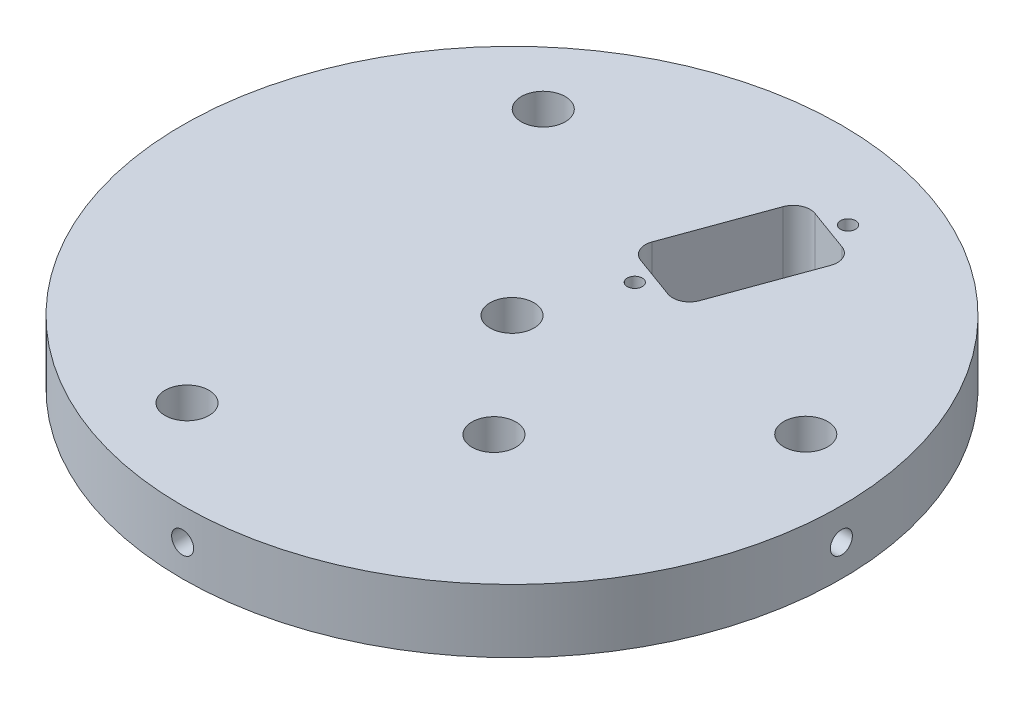
SolidWorks part; units mm, degrees
material "6061-T6 (SS)"
ref_plane "Front Plane" through (0, 0, 0) normal (0, 0, 1) x (1, 0, 0)
ref_plane "Top Plane" through (0, 0, 0) normal (0, 1, 0) x (1, 0, 0)
ref_plane "Right Plane" through (0, 0, 0) normal (1, 0, 0) x (0, 0, -1)
sketch "Sketch1" plane through (0, 0, 0) normal (0, 1, 0) x (1, 0, 0)
  line L0 (0, 0) -> (-50.3682, 60.0265)
  line L1 (0, 0) -> (50.3682, 60.0265)
  line L2 (0, 0) -> (0, 72.1431) construction
  circle A0 centre (0, 0) radius 78.359
  circle A1 centre (0, 0) radius 51.1048
  circle A2 centre (0, 0) radius 76.1746
  dimension "D1" = 156.718
  dimension "D2" = 102.2096
  dimension "D3" = 152.3492
  dimension "D4" = 80
extrude "Boss-Extrude1" add sketch "Sketch1" along normal blind 25.4 contours L2 A2 L1 A0 | L2 A1 L1 A2 | L2 A2 L1 A1 | L2 A0 L1 A2 | A2 L2 A1 L0 | A0 L2 A2 L0 | A2 L2 A0 L0 | A1 L2 A2 L0 region at (-22.4568, 0, 48.1587) region at (-40.1048, 0, -49.4238) region at (-33.0764, 0, 70.9325) region at (-48.8794, 0, -59.85)
ref_plane "Plane1" through (0, 12.7, 0) normal (0, 1, 0) x (1, 0, 0)
sketch "Sketch6" plane through (0, 25.4, 0) normal (0, 1, 0) x (1, 0, 0)
  circle A0 centre (0, 0) radius 49.5173
  dimension "D1" = 99.0346
extrude "Boss-Extrude5" add sketch "Sketch6" along normal blind 9.525
sketch "Sketch7" plane through (0, 0, 0) normal (0, -1, 0) x (1, 0, 0)
  circle A0 centre (0, 0) radius 49.5173
  dimension "D1" = 99.0346
extrude "Boss-Extrude6" add sketch "Sketch7" along normal blind 9.525
sketch "Sketch8" plane through (0, -9.525, 0) normal (0, -1, 0) x (1, 0, 0)
  circle A0 centre (0, 0) radius 46.99
  dimension "D1" = 93.98
ref_plane "Plane2" through (0, 0, -49.5173) normal (0, 0, -1) x (-1, 0, 0)
ref_plane "Plane5" through (0, 25.4, 0) normal (0, 1, 0) x (1, 0, 0)
ref_axis "Axis1" through (0, 0, 0) along (0, 1, 0)
ref_plane "Plane3" through (0, 34.925, 0) normal (0, 1, 0) x (1, 0, 0)
sketch "Sketch9" plane through (0, 34.925, 0) normal (0, 1, 0) x (1, 0, 0)
  line L0 (0, 0) -> (-26.8004, -73.6334) construction
  line L1 (0, 0) -> (32.0596, -38.2071) construction
  line L2 (0, 0) -> (0, -86.0416) construction
  circle A0 centre (0, 0) radius 3.3
  circle A1 centre (-13.031, -35.8023) radius 3.3
  circle A4 centre (14.1499, -16.8632) radius 3.3
  circle A5 centre (-24.4902, 29.1863) radius 3.3
  circle A6 centre (37.5212, 6.616) radius 3.3
  point P15 (-1.3039, -1.0954)
  point P18 (0, 0)
  dimension "D1" = 6.6
  dimension "D2" = 6.6
  dimension "D6" = 6.6
  dimension "D3" = 38.1
  dimension "D4" = 60
  dimension "D7" = 22.0133
  dimension "D8" = 20
extrude "Cut-Extrude6" cut sketch "Sketch9" against normal through all
sketch "Sketch10" plane through (0, 25.4, 0) normal (0, 1, 0) x (1, 0, 0)
  circle A0 centre (0, 0) radius 82.3228
extrude "Cut-Extrude7" cut sketch "Sketch10" against normal through all
hole_wizard "Tap Drill for #4-40 Tap1" positions "Sketch12" profile "Sketch13" hole size "#4-40" standard "ANSI Inch" end condition through all
sketch "Sketch12" plane through (0, 34.925, 0) normal (0, 1, 0) x (1, 0, 0)
  line L0 (0, 0) -> (18.6243, 51.1699) construction
  line L2 (0, 0) -> (-24.4902, 29.1863) construction
  circle A0 centre (0, 0) radius 14.3933 construction
  point P0 (4.9228, 13.5253)
  point P2 (13.4733, 37.0176)
  point P18 (0, 0)
  point P19 (-24.4902, 29.1863)
  dimension "D3" = 28.7867
  dimension "D1" = 60
  dimension "D2" = 25
sketch "Sketch13" plane through (4.9228, 34.925, -13.5253) normal (1, 0, 0) x (0, 0, 1)
  line L0 (0, 0) -> (0, 9.525)
  line L1 (0, 9.525) -> (1.1303, 9.525)
  line L2 (1.1303, 9.525) -> (1.1303, 0)
  line L5 (1.1303, 0) -> (0, 0)
  line L11 (0, -6.35) -> (0, 107.95) construction
  dimension "Thru Hole Dia." = 2.2606
  dimension "Thru Hole Depth" = 9.525
sketch "Sketch14" plane through (0, 34.925, 0) normal (0, 1, 0) x (1, 0, 0)
  line L0 (4.9228, 13.5253) -> (13.4733, 37.0176) construction
  line L1 (12.1824, 16.0187) -> (17.4317, 30.4411)
  line L2 (8.9269, 14.5007) -> (2.4825, 16.8462)
  line L3 (15.9137, 33.6967) -> (9.4692, 36.0423)
  line L4 (0.9644, 20.1018) -> (6.2137, 34.5242)
  arc A0 (17.4317, 30.4411) -> (15.9137, 33.6967) centre (15.0449, 31.3099) ccw
  arc A1 (9.4692, 36.0423) -> (6.2137, 34.5242) centre (8.6005, 33.6555) ccw
  arc A2 (8.9269, 14.5007) -> (12.1824, 16.0187) centre (9.7956, 16.8875) ccw
  arc A3 (2.4825, 16.8462) -> (0.9644, 20.1018) centre (3.3512, 19.2331) cw
  point P0 (5.7047, 15.6734)
  dimension "D4" = 2.54
  dimension "D5" = 2.54
  dimension "D2" = 2.286
  dimension "D3" = 11.938
extrude "Cut-Extrude9" cut sketch "Sketch14" against normal through all
ref_plane "Plane6" through (49.5173, 0, 0) normal (1, 0, 0) x (0, 0, -1)
hole_wizard "Tap Drill for M4x0.7 Tap1" positions "Sketch16" profile "Sketch17" hole size "M4x0.7" standard "ANSI Metric"
sketch "Sketch16" plane through (49.5173, 0, 0) normal (1, 0, 0) x (0, 0, -1)
  line L1 (49.5173, 34.925) -> (-49.5173, 34.925) construction
  point P0 (0, 30.1625)
  dimension "D1" = 4.7625
sketch "Sketch17" plane through (49.5173, 30.1625, 0) normal (0, 1, 0) x (0, 0, -1)
  line L0 (0, 0) -> (0, 10.6434)
  line L1 (0, 10.6434) -> (1.65, 9.652)
  line L2 (1.65, 9.652) -> (1.65, 0)
  line L5 (1.65, 0) -> (0, 0)
  line L10 (0, 10.6434) -> (-1.65, 9.652) construction
  line L11 (0, -6.35) -> (0, 107.95) construction
  dimension "Hole Dia." = 3.3
  dimension "Hole Depth" = 9.652
  dimension "Drill Angle" = 118
pattern_circular "CirPattern1" count 4 over 360 about axis through (0, 34.925, 0) along (0, 1, 0) of "Tap Drill for M4x0.7 Tap1"
equation "\"AB_Coupler_OD_Length\"= 1in"
equation "\"AB_Coupling_Section_Length\"= 0.375in"
equation "\"AB_Coupler_Length\"= \"AB_Coupler_OD_Length\" + \"AB_Coupling_Section_Length\" * 2"
equation "\"Cutout_Angle\" = 60"
equation "\"AB_Coupler_Num_Screws\"= 4"
equation "\"Num_Cutouts\" = 4"
equation "\"AB_Coupler_OD\"= 4.024in"
equation "\"AB_Coupler_ID\"= 3.7in"
equation "\"AB_Coupler_Surface_Diameter\"= 3.899in"
equation "\"D2@Sketch1\"= \"Body_Tube_OD\""
equation "\"AB_Coupling_Screw_Diameter\"= 0.1065in"
equation "\"Aft_Section_Length\" = 30in"
equation "\"Mid_Coupler_Length\" = 12in"
equation "\"Lead_Screw_Dist\" = 2in"
equation "\"Lead_Screw_Diam\" = 0.375in"
equation "\"Lead_Screw_Length\" = \"Mid_Coupler_Length\" + 2*0.375in + 2*0.5in"
equation "\"Paddle_Pin_Offset\" = 0.25in"
equation "\"Paddle_Pin_Radius\" = 2.25*2/3in"
equation "\"D1@Sketch6\"=\"AB_Coupler_Surface_Diameter\""
equation "\"D1@Boss-Extrude5\"=\"AB_Coupling_Section_Length\""
equation "\"D1@Sketch7\"=\"AB_Coupler_Surface_Diameter\""
equation "\"D1@Boss-Extrude6\"=\"AB_Coupling_Section_Length\""
equation "\"D1@Sketch8\"=\"AB_Coupler_ID\""
equation "\"D3@Sketch9\"=\"Paddle_Pin_Radius\""
equation "\"Motor_OD\" = 54mm"
equation "\"AB_Paddle_Height\" = 0.375in"
equation "\"AB_Central_Bushing_Length\" = 0.75in"
equation "\"Paddle_Gear_OD\" = 3.2in"
equation "\"Fwd_BKHD_From_Top\" = 18in"
equation "\"Fin_Thickness\" = 0.118in"
equation "\"DB9_Hole_Dist\" = 25mm"
equation "\"D2@Sketch12\"=\"DB9_Hole_Dist\""
equation "\"Drive_Gear_OD\" = 1.7*2/3in"
equation "\"D3@Sketch12\"=\"Drive_Gear_OD\""
equation "\"DB9_Relief_Width\" = 0.47in"
equation "\"D3@Sketch14\"=\"DB9_Relief_Width\""
equation "\"DB9_Relief_Hole_Offset\" = 0.09in"
equation "\"D2@Sketch14\"=\"DB9_Relief_Hole_Offset\""
equation "\"D1@Sketch14\"=\"DB9_Relief_Hole_Offset\""
equation "\"Airbrakes_Wire_Hole_Dia\" = 0.25in"
equation "\"Airbrakes_Wire_Hole_Dist\" = 1.1in"
equation "\"Servo_Gear_Offset\" = 0.5in"
equation "\"Motor_Length\" = 401mm"
equation "\"Body_Tube_OD\"= 4.024in"
equation "\"Body_Tube_ID\"= 3.90in"
equation "\"Coupler_OD\" = 3.899in"
equation "\"Coupler_ID\" = 3.755in"
equation "\"Fwd_Section_Length\" = 25in"
equation "\"Mid_Section_Length\" = 6in"
equation "\"Aft_Upper_Tube_Length\" = 10in"
equation "\"Aft_Lower_Tube_Length\" = 18in"
equation "\"Nosecone_Coupler_Length\" = 5in"
equation "\"Avionics_Bulkhead_Thickness\" = 0.25in"
equation "\"Avionics_Bulkhead_Lip\" = 0.125in"
equation "\"Avionics_Board_Length\" = \"Mid_Coupler_Length\" - 2*\"Avionics_Bulkhead_Lip\""
equation "\"Lead_Screw_Hole_Diam\" = (27/64)*1in"
equation "\"Centering_Ring_Cutout_Dia\"=1.5in"
equation "\"D7@Sketch9\"=\"Drive_Gear_OD\"/2+.3"
equation "\"D1@Sketch16\"=.375/2"
